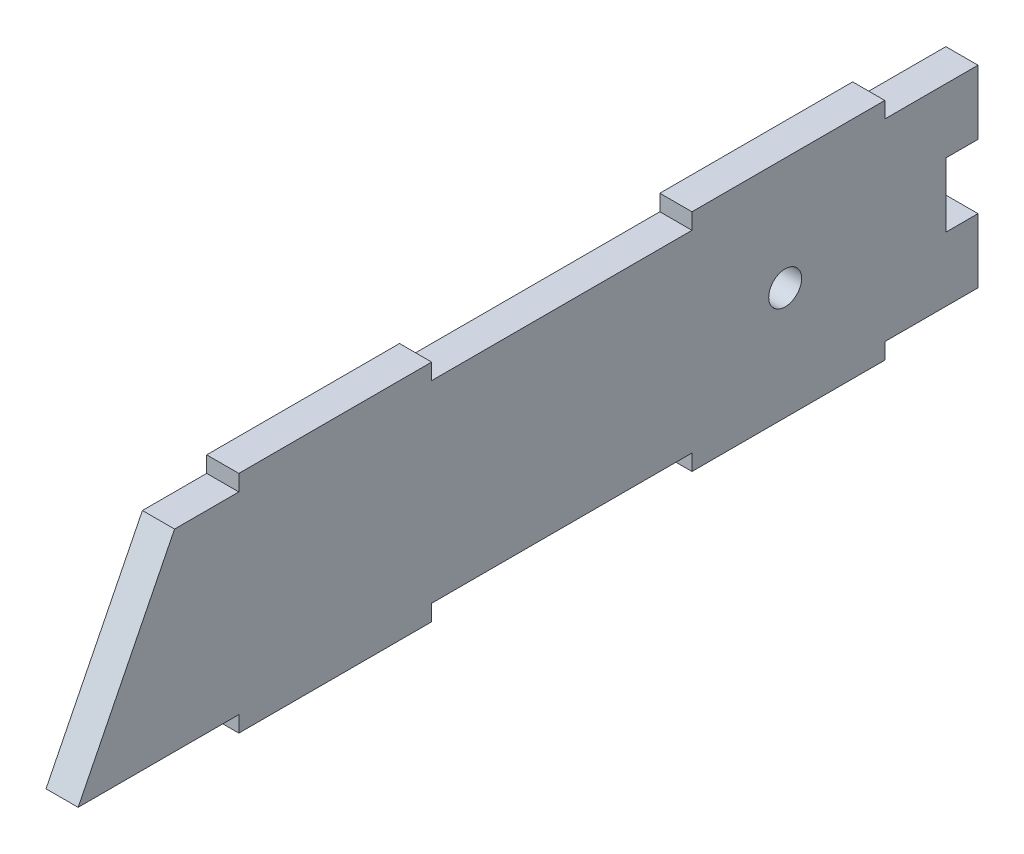
SolidWorks part; units mm, degrees
material "7050-T73510"
ref_plane "Front Plane" through (0, 0, 0) normal (0, 0, 1) x (1, 0, 0)
ref_plane "Top Plane" through (0, 0, 0) normal (0, 1, 0) x (1, 0, 0)
ref_plane "Right Plane" through (0, 0, 0) normal (1, 0, 0) x (0, 0, -1)
sketch "Sketch1" plane through (0, 0, 0) normal (1, 0, 0) x (0, 0, -1)
  line L1 (-177.8, -38.1) -> (177.8, -38.1)
  line L2 (-177.8, -38.1) -> (-177.8, 38.1)
  line L3 (-177.8, 38.1) -> (177.8, 38.1)
  line L4 (177.8, -38.1) -> (177.8, 38.1)
  line L5 (-177.8, -38.1) -> (177.8, 38.1) construction
  line L6 (-177.8, 38.1) -> (177.8, -38.1) construction
  point P0 (0, 0)
  dimension "D1" = 355.6
  dimension "D2" = 76.2
extrude "Boss-Extrude1" add sketch "Sketch1" along normal blind 12.7
sketch "Sketch2" plane through (12.7, 0, 0) normal (1, 0, 0) x (0, 0, -1)
  line L0 (-177.8, -38.1) -> (-139.7, 38.1)
  line L1 (177.8, 38.1) -> (-177.8, 38.1) construction
  dimension "D1" = 38.1
extrude "Cut-Extrude1" cut sketch "Sketch2" against normal through all and the other way through all
sketch "Sketch3" plane through (0, 0, 0) normal (-1, 0, 0) x (0, 0, 1)
  line L0 (177.8, -38.1) -> (-177.8, -38.1) construction
  line L1 (-140.97, -38.1) -> (-64.77, -38.1)
  line L2 (-140.97, -38.1) -> (-140.97, -44.45)
  line L3 (-140.97, -44.45) -> (-64.77, -44.45)
  line L4 (-64.77, -38.1) -> (-64.77, -44.45)
  line L5 (-177.8, -38.1) -> (-177.8, 38.1) construction
  line L6 (38.1, -38.1) -> (114.3, -38.1)
  line L7 (38.1, -38.1) -> (38.1, -44.45)
  line L8 (38.1, -44.45) -> (114.3, -44.45)
  line L9 (114.3, -38.1) -> (114.3, -44.45)
  line L10 (-177.8, 38.1) -> (139.7, 38.1) construction
  line L11 (-140.97, 38.1) -> (-64.77, 38.1)
  line L12 (-140.97, 38.1) -> (-140.97, 44.45)
  line L13 (-140.97, 44.45) -> (-64.77, 44.45)
  line L14 (-64.77, 38.1) -> (-64.77, 44.45)
  line L16 (38.1, 38.1) -> (114.3, 38.1)
  line L17 (38.1, 38.1) -> (38.1, 44.45)
  line L18 (38.1, 44.45) -> (114.3, 44.45)
  line L19 (114.3, 38.1) -> (114.3, 44.45)
  dimension "D1" = 76.2
  dimension "D2" = 6.35
  dimension "D3" = 76.2
  dimension "D4" = 6.35
  dimension "D5" = 36.83
  dimension "D6" = 215.9
  dimension "D7" = 76.2
  dimension "D8" = 6.35
  dimension "D9" = 6.35
  dimension "D10" = 76.2
extrude "Boss-Extrude2" add sketch "Sketch3" against normal blind 12.7
sketch "Sketch4" plane through (0, 0, 0) normal (-1, 0, 0) x (0, 0, 1)
  line L0 (-177.8, -38.1) -> (-177.8, 38.1) construction
  line L1 (-177.8, 12.7) -> (-165.1, 12.7)
  line L2 (-177.8, 12.7) -> (-177.8, -12.7)
  line L3 (-177.8, -12.7) -> (-165.1, -12.7)
  line L4 (-165.1, 12.7) -> (-165.1, -12.7)
  line L5 (-140.97, -38.1) -> (-177.8, -38.1) construction
  line L6 (-177.8, 38.1) -> (-140.97, 38.1) construction
  dimension "D1" = 25.4
  dimension "D2" = 25.4
  dimension "D3" = 12.7
extrude "Cut-Extrude2" cut sketch "Sketch4" against normal through all
sketch "Sketch5" plane through (0, 0, 0) normal (-1, 0, 0) x (0, 0, 1)
  line L0 (-165.1, -12.7) -> (-165.1, 12.7) construction
  line L1 (-140.97, -38.1) -> (-177.8, -38.1) construction
  circle A0 centre (-101.6, 0) radius 6.5
  dimension "D1" = 63.5
  dimension "D3" = 13
  dimension "D2" = 38.1
extrude "Cut-Extrude3" cut sketch "Sketch5" against normal through all
